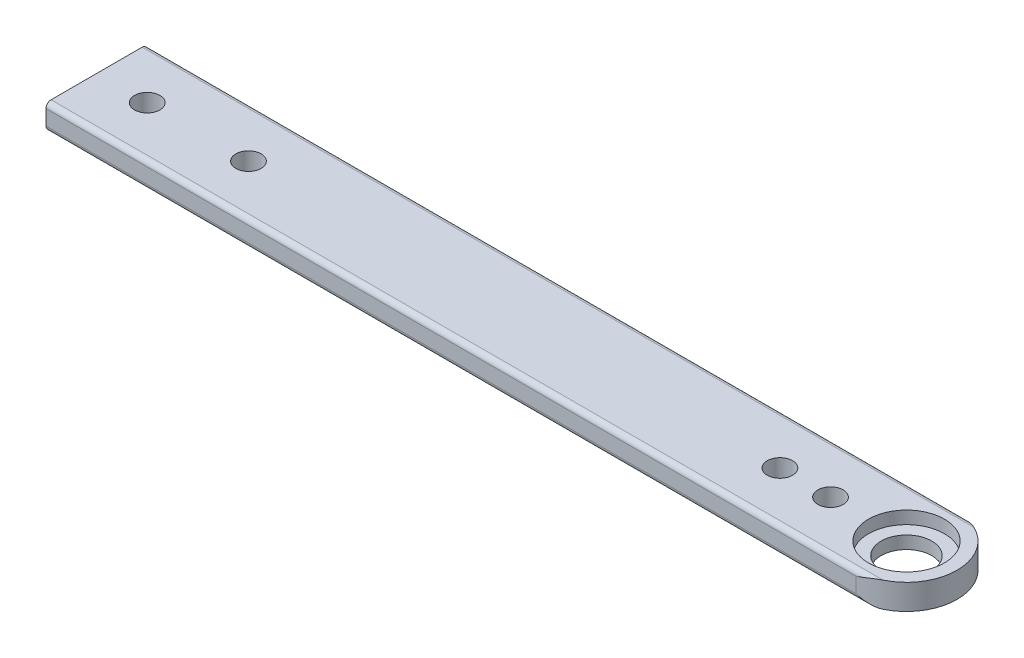
SolidWorks part; units mm, degrees
material "Plain Carbon Steel"
ref_plane "Front Plane" through (0, 0, 0) normal (0, 0, 1) x (1, 0, 0)
ref_plane "Top Plane" through (0, 0, 0) normal (0, 1, 0) x (1, 0, 0)
ref_plane "Right Plane" through (0, 0, 0) normal (1, 0, 0) x (0, 0, -1)
sketch "Sketch1" plane through (0, 0, 0) normal (0, 1, 0) x (1, 0, 0)
  line L1 (107.95, -12.7) -> (-107.95, -12.7)
  line L2 (107.95, -12.7) -> (107.95, 12.7)
  line L3 (107.95, 12.7) -> (-107.95, 12.7)
  line L4 (-107.95, -12.7) -> (-107.95, 12.7)
  line L5 (107.95, -12.7) -> (-107.95, 12.7) construction
  line L6 (107.95, 12.7) -> (-107.95, -12.7) construction
  point P0 (0, 0)
  dimension "D1" = 25.4
  dimension "D2" = 215.9
extrude "Boss-Extrude1" add sketch "Sketch1" along normal blind 6.35
fillet "Fillet1" radius 1.27 4 edges at (0, 0, -12.7) (0, 6.35, -12.7) (0, 0, 12.7) (0, 6.35, 12.7)
sketch "Sketch2" plane through (0, 6.35, 0) normal (0, 1, 0) x (1, 0, 0)
  line L0 (-107.95, 0) -> (107.95, 0) construction
  line L1 (-107.95, 11.43) -> (-107.95, -11.43) construction
  line L2 (107.95, -11.43) -> (107.95, 11.43) construction
  circle A0 centre (-95.25, 0) radius 3.175
  circle A3 centre (95.25, 0) radius 6.35
  circle A7 centre (-69.85, 0) radius 3.175
  dimension "D1" = 12.7
  dimension "D4" = 6.35
  dimension "D2" = 190.5
  dimension "D3" = 12.7
  dimension "D5" = 2
extrude "Cut-Extrude1" cut sketch "Sketch2" against normal through all
sketch "Sketch3" plane through (0, 6.35, 0) normal (0, 1, 0) x (1, 0, 0)
  circle A0 centre (95.25, 0) radius 9.525
  dimension "D1" = 19.05
extrude "Cut-Extrude2" cut sketch "Sketch3" against normal blind 3.175
sketch "Sketch4" plane through (0, 6.35, 0) normal (0, 1, 0) x (1, 0, 0)
  line L0 (-107.95, 0) -> (107.95, 0) construction
  circle A0 centre (76.2, 0) radius 3.175
  circle A2 centre (63.5, 0) radius 3.175
  dimension "D3" = 6.35
  dimension "D1" = 19.05
  dimension "D2" = 12.7
extrude "Cut-Extrude3" cut sketch "Sketch4" against normal through all
sketch "Sketch5" plane through (0, 6.35, 0) normal (0, 1, 0) x (1, 0, 0)
  line L0 (-107.95, 12.7) -> (107.95, 12.7) construction
  line L1 (107.95, -11.43) -> (107.95, 11.43) construction
  line L2 (107.95, -12.7) -> (-107.95, -12.7) construction
  line L4 (82.55, -12.7) -> (107.95, -12.7)
  line L5 (82.55, -12.7) -> (82.55, 12.7)
  line L6 (82.55, 12.7) -> (107.95, 12.7)
  line L7 (107.95, -12.7) -> (107.95, 12.7)
  line L8 (82.55, -12.7) -> (107.95, 12.7) construction
  line L9 (82.55, 12.7) -> (107.95, -12.7) construction
  circle A0 centre (95.25, 0) radius 12.7
  line M11 (107.95, -11.43) -> (107.95, 11.43)
  line M12 (107.95, 11.43) -> (-107.95, 11.43)
  line M14 (-107.95, -11.43) -> (107.95, -11.43)
extrude "Cut-Extrude4" cut sketch "Sketch5" against normal through all contours A0 L7 M12 | A0 L7 L6 M12 | A0 M14 M11 | A0 L4 L7 M14 region at (103.3706, 6.35, 12.1169) region at (105.9682, 6.35, 8.7575) region at (105.9682, 6.35, -8.7575) region at (103.3706, 6.35, -12.1169)
